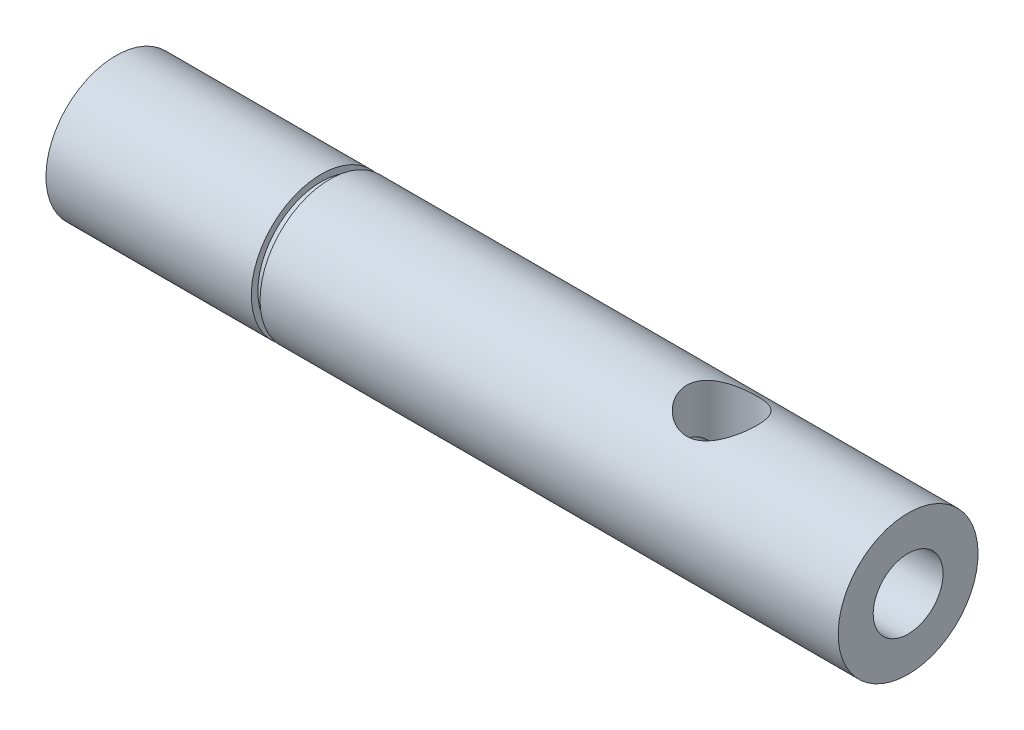
SolidWorks part; units mm, degrees
material "6063-T6"
ref_plane "Front" through (0, 0, 0) normal (0, 0, 1) x (1, 0, 0)
ref_plane "Top" through (0, 0, 0) normal (0, 1, 0) x (1, 0, 0)
ref_plane "Right" through (0, 0, 0) normal (1, 0, 0) x (0, 0, -1)
ref_axis "Axis1" through (0, 0, 55) along (0, 0, -1)
sketch "Sketch1" plane through (0, 0, 0) normal (0, 0, 1) x (1, 0, 0)
  line L0 (-53.975, 0) -> (53.975, 0) construction
  line L1 (53.975, 9.525) -> (-53.975, 9.525)
  line L2 (53.975, 9.525) -> (53.975, 4.7625)
  line L3 (53.975, 4.7625) -> (35.2472, 4.7625)
  line L4 (35.2472, 4.7625) -> (29.7343, 3.156)
  line L5 (29.7343, 3.156) -> (-27.7937, 3.156)
  line L6 (-27.7937, 3.156) -> (-35.9404, 6.985)
  line L7 (-35.9404, 6.985) -> (-53.975, 6.985)
  line L8 (-53.975, 6.985) -> (-53.975, 9.525)
  point P4 (0, 0)
  point P14 (19.9185, 8.2667)
  point P15 (23.8554, 8.4449)
  point P16 (-50.7954, 19.221)
  point P17 (-50.7727, 19.0562)
  dimension "D1" = 107.95
  dimension "D2" = 19.05
  dimension "D3" = 9.525
  dimension "D4" = 13.97
  dimension "D5" = 6.3121
  dimension "D6" = 29.7343
  dimension "D7" = 35.2472
  dimension "D8" = 27.7937
  dimension "D9" = 35.9404
revolve "Revolve1" add sketch "Sketch1" angle 360 about L0
ref_plane "Plane1" through (0, 9.525, 0) normal (0, 1, 0) x (1, 0, 0)
sketch "Sketch2" plane through (0, 9.525, 0) normal (0, 1, 0) x (1, 0, 0)
  line L0 (-53.975, 0) -> (53.975, 0) construction
  line L1 (-53.975, 9.525) -> (-53.975, -9.525) construction
  line L2 (53.975, -9.525) -> (53.975, 9.525) construction
  circle A0 centre (28.575, 0) radius 4.7625
  dimension "D1" = 9.525
  dimension "D2" = 25.4
extrude "Cut-Extrude1" cut sketch "Sketch2" against normal blind 7.62
sketch "Sketch3" plane through (0, 0, 0) normal (0, 1, 0) x (1, 0, 0)
  line L0 (-53.975, 0) -> (53.975, 0) construction
  line L1 (-53.975, 9.525) -> (-53.975, -9.525) construction
  line L2 (53.975, -9.525) -> (53.975, 9.525) construction
  line L3 (-25.4, 9.525) -> (-25.4, -9.525) construction
  line L4 (-53.975, -9.525) -> (53.975, -9.525) construction
  line L6 (-25.9957, 10.4163) -> (-24.8043, 10.4163)
  line L7 (-25.9957, 10.4163) -> (-25.9957, 8.6337)
  line L8 (-25.9957, 8.6337) -> (-24.8043, 8.6337)
  line L9 (-24.8043, 10.4163) -> (-24.8043, 8.6337)
  line L10 (-25.9957, 10.4163) -> (-24.8043, 8.6337) construction
  line L11 (-25.9957, 8.6337) -> (-24.8043, 10.4163) construction
  point P11 (-25.4, 0)
  dimension "D1" = 28.575
  dimension "D2" = 24.8043
  dimension "D3" = 8.6337
revolve "Cut-Revolve1" cut sketch "Sketch3" angle 360 about L0
